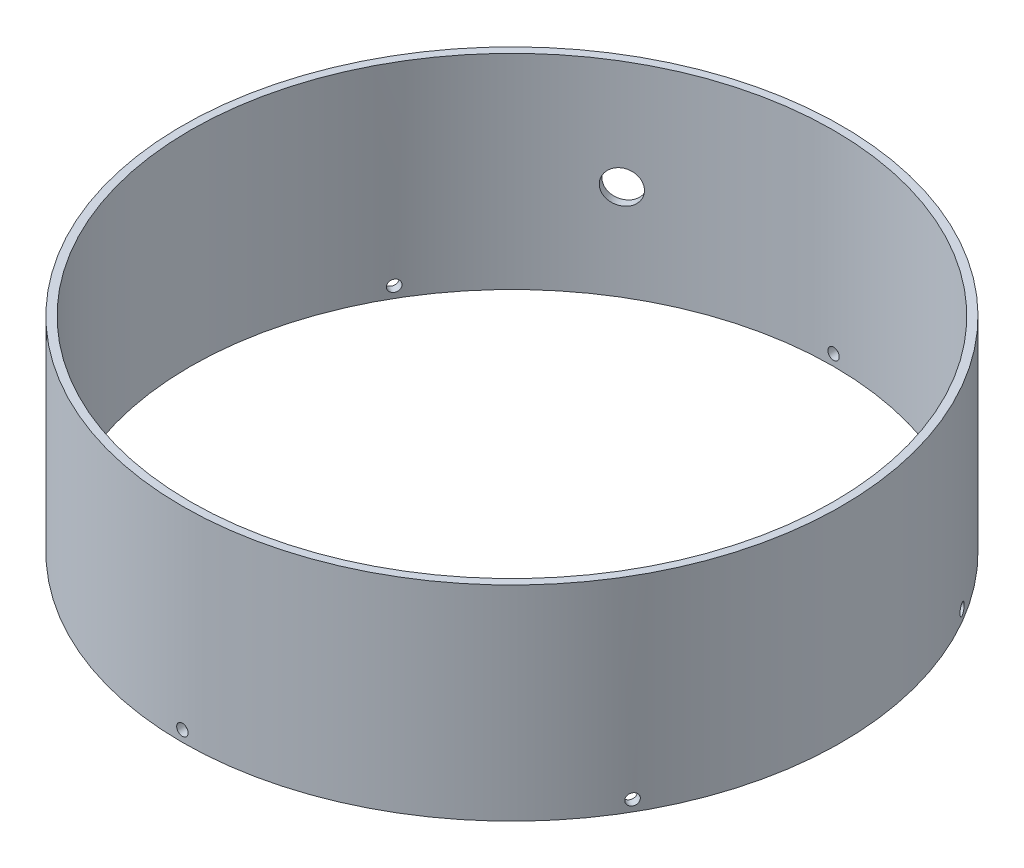
SolidWorks part; units mm, degrees
material "E-Glass Fiber"
ref_plane "Front Plane" through (0, 0, 0) normal (0, 0, 1) x (1, 0, 0)
ref_plane "Top Plane" through (0, 0, 0) normal (0, 1, 0) x (1, 0, 0)
ref_plane "Right Plane" through (0, 0, 0) normal (1, 0, 0) x (0, 0, -1)
sketch "Sketch2" plane through (0, 0, 0) normal (0, 1, 0) x (1, 0, 0)
  circle A0 centre (0, 0) radius 76.2
  circle A1 centre (0, 0) radius 74.3712
  dimension "D1" = 152.4
extrude "Boss-Extrude1" add sketch "Sketch2" along normal blind 47.2948 contours A0 A1 region at (-75.9845, 0, 0)
sketch "Sketch3" plane through (0, 0, 0) normal (0, 0, 1) x (1, 0, 0)
  circle A0 centre (0, 2.54) radius 1.3208
  dimension "D1" = 2.6416
  dimension "D2" = 2.54
extrude "Cut-Extrude1" cut sketch "Sketch3" along normal up to surface (76.1886 mm away) contours A0 region at (0, 2.54, 0) up to face at (0, 47.2948, 76.2)
pattern_circular "CirPattern1" count 6 over 360 about axis through (0, 47.2948, 0) along (0, -1, 0) of "Cut-Extrude1"
sketch "Sketch4" plane through (0, 0, 0) normal (0, 1, 0) x (1, 0, 0)
  line L0 (0, 0) -> (27.9466, 0) construction
  line L1 (0, 0) -> (-22.5703, 37.5632) construction
  dimension "D1" = 121
ref_plane "Plane1" through (0, 0, 0) normal (-0.515, 0, -0.8572) x (-0.8572, 0, 0.515)
sketch "Sketch5" plane through (0, 0, 0) normal (-0.515, 0, -0.8572) x (-0.8572, 0, 0.515)
  circle A0 centre (0, 22.098) radius 3.81
  dimension "D1" = 7.62
  dimension "D2" = 22.098
extrude "Cut-Extrude2" cut sketch "Sketch5" along normal through all contours A0 region at (0, 22.098, 0)
equation "\"Middle Coupler Inner Daimeter\"= 3.875in"
equation "\"Middle Coupler  Wall Thickness\" = 0.25in"
equation "\"Middle Coupler Bottom Thickness\"= 0.2in"
equation "\"Bearing Rail Offset\"= 0.45in"
equation "\"3-56 UNF Tap\"= 0.089in"
equation "\"3-48 Tap\"= 0.079in"
equation "\"3-56 UNF Clearance\"= 0.104in"
equation "\"3-48 Clearance\" = 0.104in"
equation "\"Ball Bearing Distance\"= 0.03in"
equation "\"TCA Outer Diameter\" = 6in"
equation "\"Interstage Aeroframe Wall Thickness\" = 0.072in"
equation "\"Compression Spring OD\"= 0.42in"
equation "\"10-24 Tap\"= 0.157in"
equation "\"10-24 Clearance\"= 0.196in"
equation "\"Lower Stage Fuselage Wall Thickness\" = 0.25in"
equation "\"6-32 Tap\" = 0.107in"
equation "\"6-32 Clearance\" = 0.144"
equation "\"1/4-20 Tap\" = 0.201in"
equation "\"12-24 Tap\" = 0.177in"
equation "\"D1@Sketch2\"=\"TCA Outer Diameter\""
equation "\"D1@Sketch3\"=\"3-48 Clearance\""
equation "\"D1@Boss-Extrude1\"=2.167000in - 0.05-0.255"
equation "\"D2@Sketch5\"=1.000000in-0.13"
